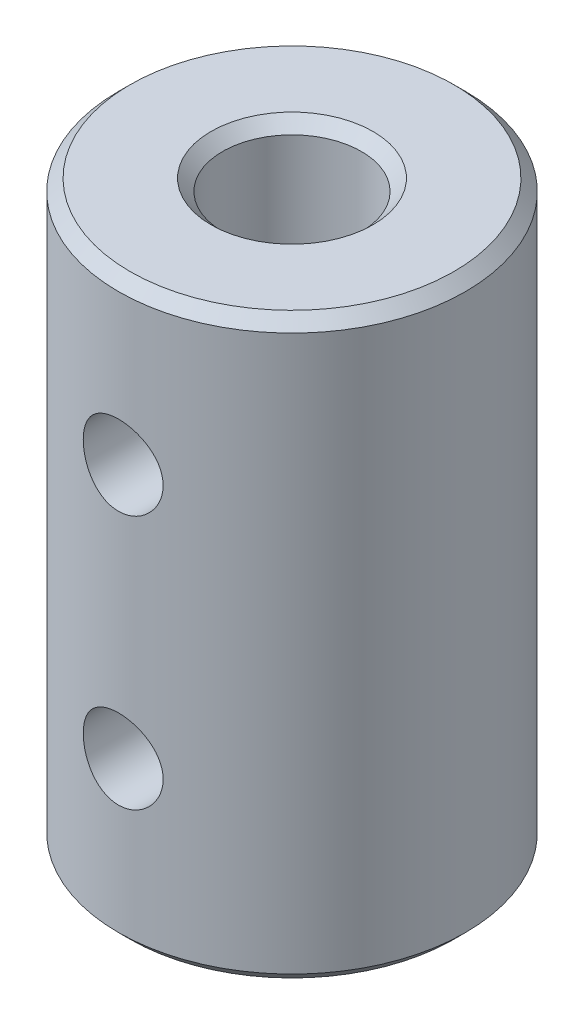
SolidWorks part; units mm, degrees
material "6061-T4 (SS)"
ref_plane "Front Plane" through (0, 0, 0) normal (0, 0, 1) x (1, 0, 0)
ref_plane "Top Plane" through (0, 0, 0) normal (0, 1, 0) x (1, 0, 0)
ref_plane "Right Plane" through (0, 0, 0) normal (1, 0, 0) x (0, 0, -1)
sketch "Sketch1" plane through (0, 0, 0) normal (0, 1, 0) x (1, 0, 0)
  circle A0 centre (0, 0) radius 3
  circle A1 centre (0, 0) radius 7.5
  dimension "D1" = 6
  dimension "D2" = 15
extrude "Boss-Extrude1" add sketch "Sketch1" along normal blind 25
chamfer "Chamfer1" distance 0.5 angle 45 4 edges at (0, 0, 3) (0, 0, 7.5) (0, 25, 3) (0, 25, 7.5)
ref_plane "Plane1" through (0, 0, 19.05) normal (0, 0, 1) x (1, 0, 0)
hole_wizard "#8-32 Tapped Hole1" positions "Sketch3" profile "Sketch4" tap size "#8-32" standard "ANSI Inch"
sketch "Sketch3" plane through (0, 0, 19.05) normal (0, 0, 1) x (1, 0, 0)
  line L0 (-7, 0) -> (7, 0) construction
  point P0 (0, 18)
  point P2 (0, 7)
  dimension "D1" = 7
  dimension "D2" = 11
cosmetic thread "Hole Thread1"
cosmetic thread "Hole Thread2"
sketch "Sketch4" plane through (0, 18, 19.05) normal (1, 0, 0) x (0, -1, 0)
  line L0 (0, 0) -> (0, 19.0378)
  line L1 (0, 19.0378) -> (1.7272, 18)
  line L2 (1.7272, 18) -> (1.7272, 0)
  line L5 (1.7272, 0) -> (0, 0)
  line L10 (0, 19.0378) -> (-1.7272, 18) construction
  line L11 (0, -6.35) -> (0, 107.95) construction
  dimension "Tap Drill Dia." = 3.4544
  dimension "Tap Drill Depth" = 18
  dimension "Drill Angle" = 118
